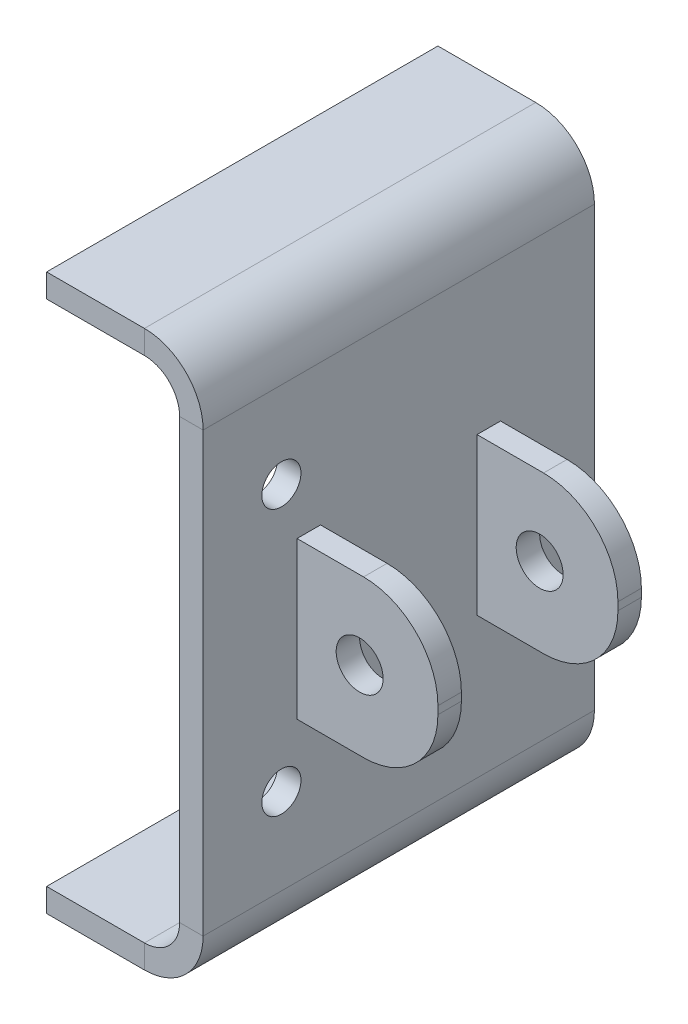
SolidWorks part; units mm, degrees
note: The reader was unsure of these and kept them because the rebuilt part matched: flange length of "Edge-Flange1".
ref_plane "Front Plane" through (0, 0, 0) normal (1, 0, 0) x (0, 1, 0)
ref_plane "Top Plane" through (0, 0, 0) normal (0, 0, 1) x (0, 1, 0)
ref_plane "Right Plane" through (0, 0, 0) normal (0, 1, 0) x (-1, 0, 0)
sketch "Sketch1" plane through (0, 0, 0) normal (1, 0, 0) x (0, 1, 0)
  line L1 (-32.5, -25) -> (32.5, -25)
  line L2 (-32.5, -25) -> (-32.5, 25)
  line L3 (-32.5, 25) -> (32.5, 25)
  line L4 (32.5, -25) -> (32.5, 25)
  line L5 (-32.5, -25) -> (32.5, 25) construction
  line L6 (-32.5, 25) -> (32.5, -25) construction
  point P0 (0, 0)
  dimension "D1" = 50
  dimension "D2" = 65
base flange "Base-Flange1" sketch "Sketch1" thickness 3 reverse thickness direction yes parameters "D1"=0.7366
edge flange "Edge-Flange1" sketch "Sketch10" flange profiles "Sketch10", "Sketch11" flange angle 90 flange length 20 flange position material outside bend radius 4.5 thickness 3 relief rectangular parameters "D6"=10, "D8"=1
sketch "Sketch10" plane through (0, 32.5, 0) normal (0, 1, 0) x (0, 0, -1)
  line L2 (-25, 0) -> (-25, 17)
  line L3 (-25, 17) -> (25, 17)
  line L4 (25, 17) -> (25, 0)
  line L7 (25, 0) -> (-25, 0) construction
  line L8 (25, 0) -> (-25, 0)
sketch "Sketch11" plane through (0, -32.5, 0) normal (0, -1, 0) x (0, 0, 1)
  line L0 (25, 0) -> (-25, 0) construction
  line L1 (25, 0) -> (-25, 0)
  line L2 (-25, 0) -> (-25, 17)
  line L3 (-25, 17) -> (25, 17)
  line L4 (25, 17) -> (25, 0)
bend "EdgeBend1" bend radius 4.5 bend angle 90 parameters "D5"=1
bend "EdgeBend2" bend radius 4.5 bend angle 90 parameters "D5"=2
sketch "Sketch13" plane through (3, 0, 0) normal (1, 0, 0) x (0, 1, 0)
  line L0 (28, 25) -> (-28, 25) construction
  circle A0 centre (-17, 15) radius 2.5
  circle A1 centre (17, 15) radius 2.5
  point P5 (-14.5, -19.9604)
  point P6 (10.5105, -18.5178)
  point P7 (0, 0)
  point P10 (0, 0)
  dimension "D1" = 5
  dimension "D2" = 5
  dimension "D3" = 17
  dimension "D5" = 17
  dimension "D4" = 10
extrude "Cut-Extrude1" cut sketch "Sketch13" against normal blind 10 normal cut yes
sketch "Sketch14" plane through (3, 0, 0) normal (1, 0, 0) x (0, 1, 0)
  line L1 (10, 13) -> (-10, 13)
  line L2 (10, 13) -> (10, 10)
  line L3 (10, 10) -> (-10, 10)
  line L4 (-10, 13) -> (-10, 10)
  line L5 (10, 13) -> (-10, 10) construction
  line L6 (10, 10) -> (-10, 13) construction
  line L7 (10, -10) -> (-10, -10)
  line L8 (10, -10) -> (10, -13)
  line L9 (10, -13) -> (-10, -13)
  line L10 (-10, -10) -> (-10, -13)
  line L11 (10, -10) -> (-10, -13) construction
  line L12 (10, -13) -> (-10, -10) construction
  point P0 (0, 11.5)
  point P5 (0, -11.5)
  dimension "D1" = 20
  dimension "D2" = 20
  dimension "D3" = 3
  dimension "D4" = 3
  dimension "D5" = 10
  dimension "D6" = 10
extrude "Boss-Extrude1" add sketch "Sketch14" along normal blind 18
fillet "Fillet1" radius 9.5 4 edges at (21, 10, -11.5) (21, -10, -11.5) (21, -10, 11.5) (21, 10, 11.5)
sketch "Sketch15" plane through (0, 0, 13) normal (0, 0, 1) x (1, 0, 0)
  line L0 (21, 0.5) -> (21, -0.5) construction
  circle A0 centre (11, 0) radius 3
  dimension "D1" = 6
  dimension "D2" = 10
extrude "Cut-Extrude2" cut sketch "Sketch15" against normal blind 31 normal cut yes
sketch "Bend-Lines1" [suppressed] plane through (0, 0, 0) normal (0, 1, 0) x (1, 0, 0)
sketch "Bounding-Box1" [suppressed] plane through (0, 0, 0) normal (0, 1, 0) x (1, 0, 0)
sheet metal parameters "Sheet-Metal1" thickness 3 parameters "D1"=0.7366
flat pattern "Flat-Pattern1" [suppressed]
sketch "Bend-Lines2" plane through (0, 0, 0) normal (0, 1, 0) x (1, 0, 0)
sketch3d "Bounding-Box2" [suppressed]
  line L0 (-32.5, 32.5, 0) -> (-32.5, -32.5, 0) construction
  line L1 (32.5, 32.5, 0) -> (32.5, -32.5, 0) construction
  line L2 (-32.5, 32.5, 0) -> (32.5, 32.5, 0) construction
  line L3 (-32.5, -32.5, 0) -> (32.5, -32.5, 0) construction
sheet metal parameters "Sheet-Metal2" thickness 3 parameters "D1"=0.7366
flat pattern "Flat-Pattern1"
sketch "Bend-Lines2" plane through (0, 0, 0) normal (-1, 0, 0) x (0, 0, 1)
  line L0 (-32.5, -32.7124) -> (32.5, -32.7124) construction
  line L1 (32.5, 32.7124) -> (-32.5, 32.7124) construction
  line L2 (-32.5, -32.7124) -> (32.5, -32.7124) construction
  line L3 (32.5, 32.7124) -> (-32.5, 32.7124) construction
sketch3d "Bounding-Box2" [suppressed]
  line L0 (32.5, 49.9248, 0) -> (32.5, -49.9248, 0) construction
  line L1 (-32.5, 49.9248, 0) -> (-32.5, -49.9248, 0) construction
  line L2 (32.5, 49.9248, 0) -> (-32.5, 49.9248, 0) construction
  line L3 (32.5, -49.9248, 0) -> (-32.5, -49.9248, 0) construction
bend of the flat pattern "Flatten-<EdgeBend1>1"
bend of the flat pattern "Flatten-<EdgeBend2>1"
sheet metal parameters "Sheet-Metal3" thickness 3 parameters "D1"=0.7366
flat pattern "Flat-Pattern1"
sketch "Bend-Lines2" plane through (0, 0, 0) normal (-1, 0, 0) x (0, 0, 1)
  line L0 (-32.5, -32.7124) -> (32.5, -32.7124) construction
  line L1 (32.5, 32.7124) -> (-32.5, 32.7124) construction
  line L2 (-32.5, -32.7124) -> (32.5, -32.7124) construction
  line L3 (32.5, 32.7124) -> (-32.5, 32.7124) construction
sketch3d "Bounding-Box2" [suppressed]
  line L0 (32.5, 49.9248, 0) -> (32.5, -49.9248, 0) construction
  line L1 (-32.5, 49.9248, 0) -> (-32.5, -49.9248, 0) construction
  line L2 (32.5, 49.9248, 0) -> (-32.5, 49.9248, 0) construction
  line L3 (32.5, -49.9248, 0) -> (-32.5, -49.9248, 0) construction
bend of the flat pattern "Flatten-<EdgeBend1>1"
bend of the flat pattern "Flatten-<EdgeBend2>1"
sheet metal parameters "Sheet-Metal4" thickness 3 parameters "D1"=0.7366
flat pattern "Flat-Pattern1"
sketch "Bend-Lines2" plane through (0, 0, 0) normal (-1, 0, 0) x (0, 0, 1)
  line L0 (-32.5, -32.7124) -> (32.5, -32.7124) construction
  line L1 (32.5, 32.7124) -> (-32.5, 32.7124) construction
  line L2 (-32.5, -32.7124) -> (32.5, -32.7124) construction
  line L3 (32.5, 32.7124) -> (-32.5, 32.7124) construction
sketch3d "Bounding-Box2" [suppressed]
  line L0 (32.5, 49.9248, 0) -> (32.5, -49.9248, 0) construction
  line L1 (-32.5, 49.9248, 0) -> (-32.5, -49.9248, 0) construction
  line L2 (32.5, 49.9248, 0) -> (-32.5, 49.9248, 0) construction
  line L3 (32.5, -49.9248, 0) -> (-32.5, -49.9248, 0) construction
bend of the flat pattern "Flatten-<EdgeBend1>1"
bend of the flat pattern "Flatten-<EdgeBend2>1"
sheet metal parameters "Sheet-Metal5" thickness 3 parameters "D1"=0.7366
flat pattern "Flat-Pattern1"
sketch "Bend-Lines2" plane through (0, 0, 0) normal (-1, 0, 0) x (0, 0, 1)
  line L0 (-25, -32.7124) -> (25, -32.7124) construction
  line L1 (25, 32.7124) -> (-25, 32.7124) construction
  line L2 (-25, -32.7124) -> (25, -32.7124) construction
  line L3 (25, 32.7124) -> (-25, 32.7124) construction
sketch3d "Bounding-Box2" [suppressed]
  line L0 (25, 49.9248, 0) -> (25, -49.9248, 0) construction
  line L1 (-25, 49.9248, 0) -> (-25, -49.9248, 0) construction
  line L2 (25, 49.9248, 0) -> (-25, 49.9248, 0) construction
  line L3 (25, -49.9248, 0) -> (-25, -49.9248, 0) construction
bend of the flat pattern "Flatten-<EdgeBend1>1"
bend of the flat pattern "Flatten-<EdgeBend2>1"
